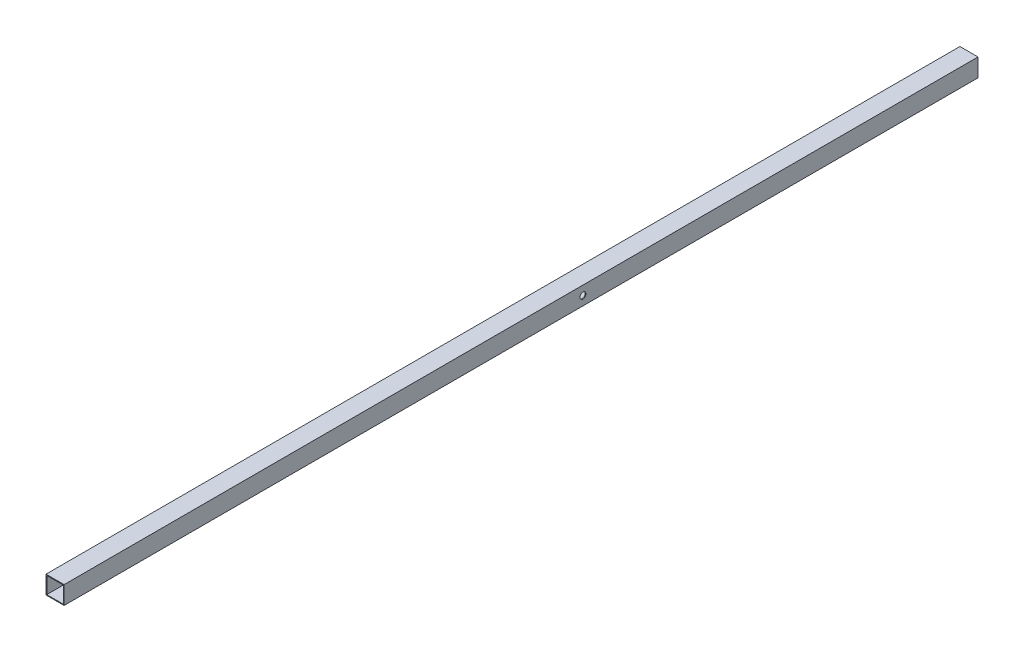
SolidWorks part; units mm, degrees
material "6061-T6 (SS)"
ref_plane "Front Plane" through (0, 0, 0) normal (0, 0, 1) x (1, 0, 0)
ref_plane "Top Plane" through (0, 0, 0) normal (0, 1, 0) x (1, 0, 0)
ref_plane "Right Plane" through (0, 0, 0) normal (1, 0, 0) x (0, 0, -1)
sketch "Sketch2" plane through (0, 0, 0) normal (0, 0, 1) x (1, 0, 0)
  line L0 (0, 19.05) -> (1.5875, 19.05) construction
  line L1 (0, 0) -> (38.1, 0)
  line L2 (0, 0) -> (0, 38.1)
  line L3 (0, 38.1) -> (38.1, 38.1)
  line L4 (38.1, 0) -> (38.1, 38.1)
  line L5 (1.5875, 1.5875) -> (36.5125, 1.5875)
  line L6 (1.5875, 1.5875) -> (1.5875, 36.5125)
  line L7 (1.5875, 36.5125) -> (36.5125, 36.5125)
  line L8 (36.5125, 1.5875) -> (36.5125, 36.5125)
  line L9 (19.05, 36.5125) -> (19.05, 38.1) construction
  line L10 (36.5125, 19.05) -> (38.1, 19.05) construction
  line L11 (19.05, 0) -> (19.05, 1.5875) construction
  dimension "D1" = 38.1
  dimension "D2" = 1.5875
  dimension "D3" = 38.1
extrude "Boss-Extrude1" add sketch "Sketch2" along normal blind 1924.05
hole_wizard "1/2 (0.5) Diameter Hole1" positions "Sketch4" profile "Sketch3" hole size "1/2" standard "ANSI Inch" end condition through all
sketch "Sketch4" plane through (0, 0, 0) normal (-1, 0, 0) x (0, 0, 1)
  line L0 (1924.05, 0) -> (0, 0) construction
  line L2 (0, 38.1) -> (0, 0) construction
  point P0 (831.85, 19.05)
  dimension "D1" = 19.05
  dimension "D2" = 831.85
sketch "Sketch3" plane through (0, 19.05, 831.85) normal (0, 1, 0) x (0, 0, 1)
  line L0 (0, 0) -> (0, 38.1)
  line L1 (0, 38.1) -> (6.35, 38.1)
  line L2 (6.35, 38.1) -> (6.35, 0)
  line L5 (6.35, 0) -> (0, 0)
  line L11 (0, -6.35) -> (0, 107.95) construction
  dimension "Thru Hole Dia." = 12.7
  dimension "Thru Hole Depth" = 38.1
